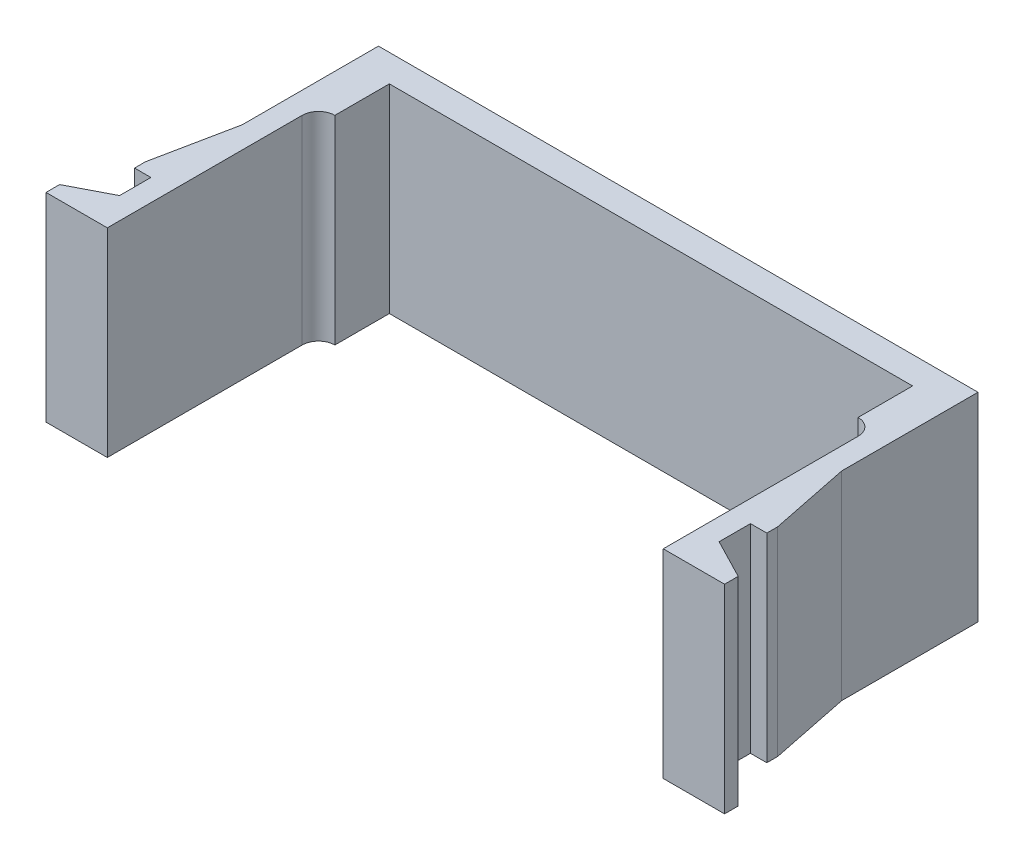
SolidWorks part; units mm, degrees
ref_plane "前视基准面" through (0, 0, 0) normal (0, 0, 1) x (1, 0, 0)
ref_plane "上视基准面" through (0, 0, 0) normal (0, 1, 0) x (1, 0, 0)
ref_plane "右视基准面" through (0, 0, 0) normal (1, 0, 0) x (0, 0, -1)
sketch "草图1" plane through (0, 0, 0) normal (0, 0, 1) x (1, 0, 0)
  line L1 (-22, -7.3) -> (22, -7.3)
  line L2 (-22, -7.3) -> (-22, 7.3)
  line L3 (-22, 7.3) -> (22, 7.3)
  line L4 (22, -7.3) -> (22, 7.3)
  line L5 (-22, -7.3) -> (22, 7.3) construction
  line L6 (-22, 7.3) -> (22, -7.3) construction
  point P0 (0, 0)
  dimension "D1" = 44
  dimension "D2" = 14.6
extrude "凸台-拉伸1" add sketch "草图1" along normal blind 2
sketch "草图2" plane through (0, 0, 2) normal (0, 0, 1) x (1, 0, 0)
  line L0 (22, 7.3) -> (-22, 7.3) construction
  line L1 (22, -7.3) -> (19.2, -7.3)
  line L2 (22, -7.3) -> (22, 7.3)
  line L3 (22, 7.3) -> (19.2, 7.3)
  line L4 (19.2, -7.3) -> (19.2, 7.3)
  dimension "D1" = 2.8
extrude "凸台-拉伸2" add sketch "草图2" along normal blind 4
sketch "草图3" plane through (0, -7.3, 0) normal (0, -1, 0) x (1, 0, 0)
  line L0 (22, 6) -> (20.4, 6)
  line L1 (19.2, 6) -> (22, 6) construction
  line L2 (20.4, 6) -> (20.4, 21.5)
  line L3 (20.4, 21.5) -> (24.9, 21.5)
  line L4 (24.9, 21.5) -> (24.9, 20.5)
  line L5 (24.9, 20.5) -> (22, 19)
  line L6 (22, 19) -> (22, 16.7)
  line L7 (22, 16.7) -> (23.2, 16.7)
  line L9 (22, 10) -> (22, 6)
  line L10 (-22, 0) -> (22, 0) construction
  line L11 (23.2, 16.7) -> (23.2, 15.9)
  line L12 (23.2, 15.9) -> (22, 10)
  point P14 (22, 19.4024)
  dimension "D1" = 1.6
  dimension "D2" = 21.5
  dimension "D3" = 4.5
  dimension "D4" = 1
  dimension "D5" = 16.7
  dimension "D6" = 1.2
  dimension "D7" = 0.8
  dimension "D8" = 10
  dimension "D9" = 19
extrude "凸台-拉伸3" add sketch "草图3" against normal up to surface (14.6 mm away) up to face at (6.4, 7.3, 2.6667)
fillet "圆角1" radius 1.2 1 edges at (20.4, 0, 6)
mirror "镜向1" about plane through (0, 0, 0) normal (1, 0, 0) of "凸台-拉伸3", "圆角1", "凸台-拉伸2"
